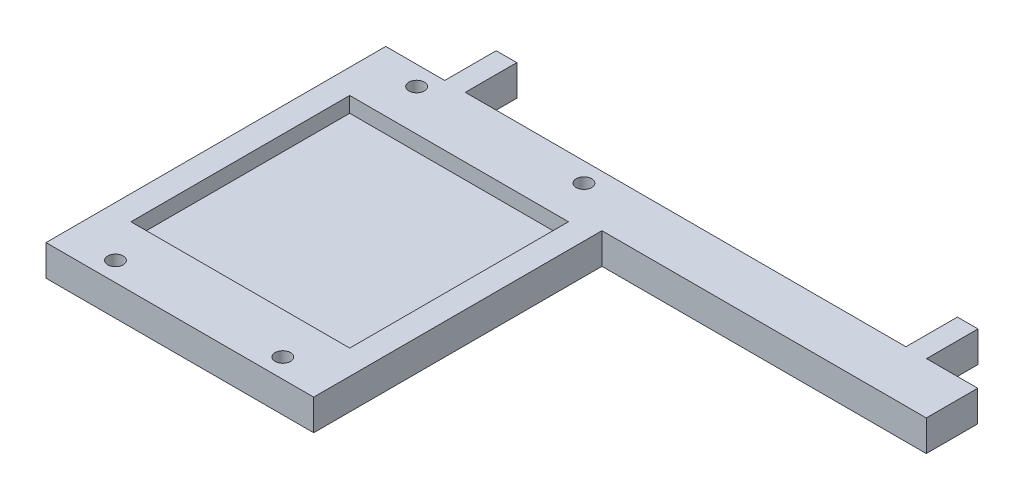
SolidWorks part; units mm, degrees
ref_plane "Front Plane" through (0, 0, 0) normal (0, 0, 1) x (1, 0, 0)
ref_plane "Top Plane" through (0, 0, 0) normal (0, 1, 0) x (1, 0, 0)
ref_plane "Right Plane" through (0, 0, 0) normal (1, 0, 0) x (0, 0, -1)
sketch "Sketch1" plane through (0, 0, 0) normal (0, 1, 0) x (1, 0, 0)
  line L1 (0, 0) -> (-52, 0)
  line L2 (0, 0) -> (0, -66)
  line L3 (0, -66) -> (-52, -66)
  line L4 (-52, 0) -> (-52, -66)
  dimension "D1" = 66
  dimension "D2" = 52
extrude "Boss-Extrude1" add sketch "Sketch1" along normal blind 6
sketch "Sketch2" plane through (0, 6, 0) normal (0, 1, 0) x (1, 0, 0)
  line L0 (-52, 0) -> (-52, -66) construction
  line L1 (-47.25, -11.75) -> (-4.75, -11.75)
  line L2 (-47.25, -11.75) -> (-47.25, -54.25)
  line L3 (-47.25, -54.25) -> (-4.75, -54.25)
  line L4 (-4.75, -11.75) -> (-4.75, -54.25)
  line L5 (-52, -66) -> (0, -66) construction
  point P6 (-47.25, -33)
  point P7 (-52, -33)
  point P8 (-26, -54.25)
  point P11 (-26, -66)
  dimension "D1" = 42.5
  dimension "D2" = 42.5
  dimension "D3" = 0
  dimension "D4" = 0
extrude "Cut-Extrude1" cut sketch "Sketch2" against normal blind 3
sketch "Sketch3" plane through (0, 6, 0) normal (0, 1, 0) x (1, 0, 0)
  line L0 (-4.75, -11.75) -> (-47.25, -11.75) construction
  line L1 (-47.25, -11.75) -> (-47.25, -54.25) construction
  line L2 (-26, 0) -> (-26, -78.9032) construction
  line L3 (0, 0) -> (-52, 0) construction
  line L4 (-52, -33) -> (19.2006, -33) construction
  line L5 (-52, 0) -> (-52, -66) construction
  circle A0 centre (-42.25, -3.75) radius 1.5
  circle A1 centre (-9.75, -3.75) radius 1.5
  circle A2 centre (-9.75, -62.25) radius 1.5
  circle A3 centre (-42.25, -62.25) radius 1.5
  dimension "D1" = 8
  dimension "D2" = 3
  dimension "D3" = 5
extrude "Cut-Extrude2" cut sketch "Sketch3" against normal blind 13
sketch "Sketch4" plane through (0, 0, 0) normal (1, 0, 0) x (0, 0, -1)
  line L0 (-66, 6) -> (0, 6) construction
  line L1 (0, 0) -> (-10, 0)
  line L2 (0, 0) -> (0, 6)
  line L3 (0, 6) -> (-10, 6)
  line L4 (-10, 0) -> (-10, 6)
  dimension "D1" = 10
extrude "Boss-Extrude2" add sketch "Sketch4" along normal blind 63
sketch "Sketch5" plane through (0, 0, 0) normal (0, 0, -1) x (-1, 0, 0)
  line L0 (-63, 6) -> (52, 6) construction
  line L1 (40.55, 6) -> (36.55, 6)
  line L2 (40.55, 6) -> (40.55, 0)
  line L3 (40.55, 0) -> (36.55, 0)
  line L4 (36.55, 6) -> (36.55, 0)
  line L5 (-63, 0) -> (52, 0) construction
  line L6 (52, 6) -> (52, 0) construction
  line L8 (-49.05, 6) -> (-53.05, 6)
  line L9 (-49.05, 6) -> (-49.05, 0)
  line L10 (-49.05, 0) -> (-53.05, 0)
  line L11 (-53.05, 6) -> (-53.05, 0)
  dimension "D1" = 4
  dimension "D2" = 11.45
  dimension "D3" = 4
  dimension "D4" = 85.6
extrude "Boss-Extrude3" add sketch "Sketch5" along normal blind 10
